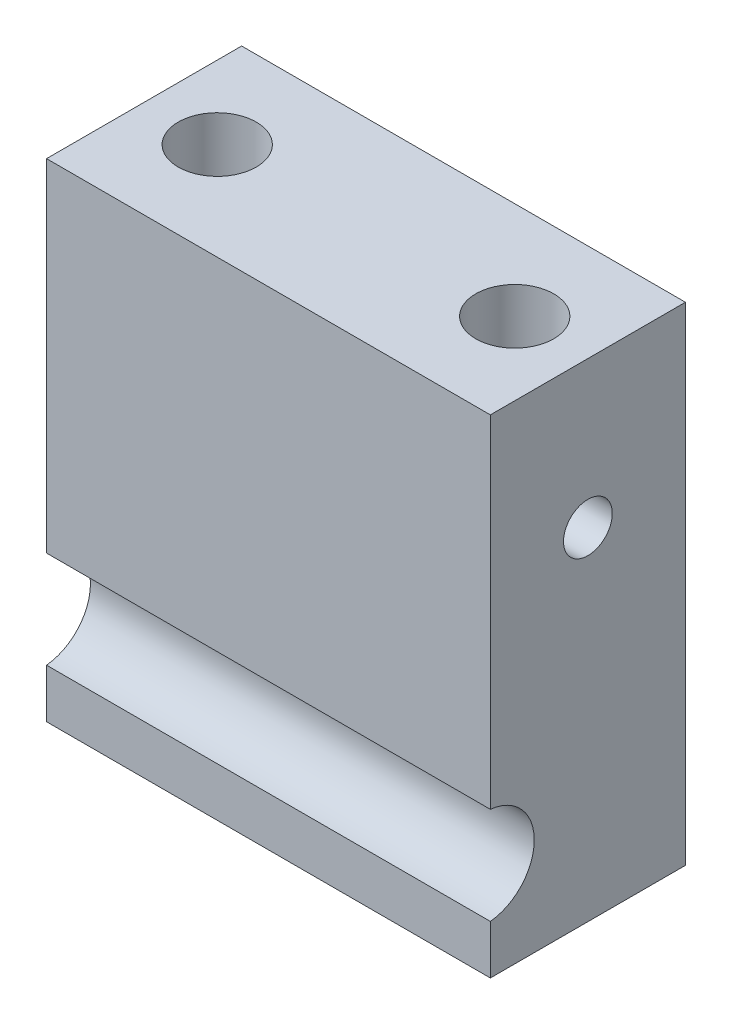
SolidWorks part; units mm, degrees
ref_plane "前视基准面" through (0, 0, 0) normal (0, 0, 1) x (1, 0, 0)
ref_plane "上视基准面" through (0, 0, 0) normal (0, 1, 0) x (1, 0, 0)
ref_plane "右视基准面" through (0, 0, 0) normal (1, 0, 0) x (0, 0, -1)
sketch "草图1" plane through (0, 0, 0) normal (0, 1, 0) x (1, 0, 0)
  line L1 (-4.55, 2) -> (4.55, 2)
  line L2 (-4.55, 2) -> (-4.55, -2)
  line L3 (-4.55, -2) -> (4.55, -2)
  line L4 (4.55, 2) -> (4.55, -2)
  line L5 (-4.55, 2) -> (4.55, -2) construction
  line L6 (-4.55, -2) -> (4.55, 2) construction
  point P0 (0, 0)
  dimension "D1" = 9.1
  dimension "D2" = 4
extrude "凸台-拉伸1" add sketch "草图1" along normal blind 10
sketch "草图2" plane through (-4.55, 0, 0) normal (-1, 0, 0) x (0, 0, 1)
  line L0 (-2, 10) -> (2, 10) construction
  line L1 (-2, 10) -> (-2, 0) construction
  circle A0 centre (0, 7) radius 0.5
  circle A1 centre (2.1, 2) radius 1
  dimension "D1" = 1
  dimension "D4" = 2
  dimension "D6" = 2.1
  dimension "D2" = 3
  dimension "D3" = 2
  dimension "D5" = 5
extrude "切除-拉伸1" cut sketch "草图2" against normal through all
sketch "草图3" plane through (0, 10, 0) normal (0, 1, 0) x (1, 0, 0)
  line L0 (4.55, 2) -> (-4.55, 2) construction
  line L1 (-4.55, 2) -> (-4.55, -2) construction
  line L2 (4.55, -2) -> (4.55, 2) construction
  circle A0 centre (3.05, 0) radius 0.8
  circle A1 centre (-3.05, 0) radius 0.8
  dimension "D1" = 1.6
  dimension "D2" = 1.6
  dimension "D6" = 1.5
  dimension "D3" = 2
  dimension "D4" = 2
  dimension "D5" = 1.5
extrude "切除-拉伸2" cut sketch "草图3" against normal blind 2
ref_axis "基准轴1" through (-3.05, 8, 0) along (0, 1, 0)
ref_axis "基准轴2" through (3.05, 8, 0) along (0, 1, 0)
ref_plane "基准面1" through (0, 0, 0) normal (0, 0, 1) x (1, 0, 0)
